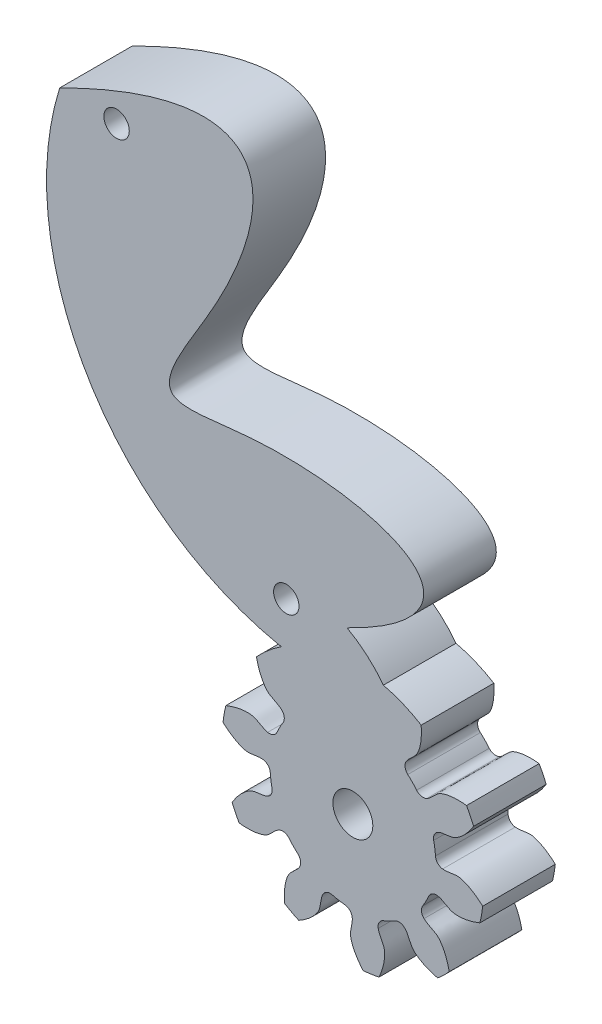
SolidWorks part; units mm, degrees
material "3003 Alaşım"
ref_plane "前视基准面" through (0, 0, 0) normal (0, 0, 1) x (1, 0, 0)
ref_plane "上视基准面" through (0, 0, 0) normal (0, 1, 0) x (1, 0, 0)
ref_plane "右视基准面" through (0, 0, 0) normal (1, 0, 0) x (0, 0, -1)
sketch "草图1" plane through (0, 0, 0) normal (0, 0, 1) x (1, 0, 0)
  line L0 (-50, 0) -> (-25, 0) construction
  line L1 (-28.7348, 74.7114) -> (-28.7348, -58.328) construction
  line L31 (-28.7348, -54.9949) -> (-28.7348, -58.328)
  line L34 (-28.7348, -66.107) -> (-16.1671, -66.107) construction
  arc A16 (-32.5692, -50.9983) -> (-62.8387, 0.35) centre (-24.3784, -11.5738) cw
  arc A17 (-23.252, -44.2645) -> (-15.0404, -59.3926) centre (-31.0005, -58.2631) cw
  arc A18 (-28.7348, -58.328) -> (-15.0404, -59.3926) centre (-22.4509, -66.107) ccw
  arc A20 (-32.5692, -50.9983) -> (-28.7348, -54.9949) centre (-32.7348, -54.9949) cw
  circle A22 centre (-22.4509, -66.107) radius 5
  circle A26 centre (-31.6201, -45.0019) radius 1.75
  circle A27 centre (-55, 0) radius 1.75
  spline S0 degree 3 poles (-62.8387, 0.35) (-32.3892, 15.6125) (-31.8503, -2.5111) (-51.8071, -30.7499) (-24.5472, -25.1943) (-0.1216, -33.0016) (-23.252, -44.2645) knots 0 0 0 0 0.423155 0.543124 0.634591 1 1 1 1
  point P9 (-25, 0)
  point P64 (-28.7348, -52.6717)
  point P69 (-2.507, 0.35)
  dimension "D4" = 3.5
  dimension "D6" = 16
  dimension "D7" = 4
  dimension "D9" = 10
  dimension "D10" = 3.5
  dimension "D3" = 25
extrude "凸台拉伸1" add sketch "草图1" along normal blind 1
extrude "凸台-拉伸1" add sketch "草图1<2>" along normal blind 10
sketch "草图1<2>" plane through (0, 0, 0) normal (0, 0, 1) x (1, 0, 0) same geometry as "草图1"
sketch "草图7" plane through (0, 0, 0) normal (0, 0, 1) x (1, 0, 0)
  line L0 (-22.4509, -66.107) -> (-22.4509, -48.107) construction
  arc A0 (-32.0748, -59.9963) -> (-32.8986, -61.5456) centre (-22.4509, -66.107) ccw
  arc A1 (-35.9543, -51.7661) -> (-41.8911, -62.9316) centre (-22.4509, -66.107) ccw
  arc A2 (-32.8986, -61.5456) -> (-34.1894, -62.2026) centre (-33.9434, -61.0895) cw
  arc A3 (-32.2519, -58.5588) -> (-32.0748, -59.9963) centre (-33.0372, -59.3852) cw
  circle A4 centre (-22.4509, -66.107) radius 14.5222 construction
  circle A5 centre (-22.4509, -66.107) radius 18 construction
  circle A6 centre (-22.4509, -66.107) radius 11.4 construction
  circle A7 centre (-22.4509, -66.107) radius 15 construction
  spline S0 degree 3 poles (-32.2519, -58.5588) (-32.7705, -58.066) (-33.6057, -57.8737) (-34.2019, -57.3264) (-34.2828, -57.24) (-34.3453, -57.1694) (-34.4147, -57.0856) (-34.4903, -56.9882) (-34.5713, -56.8768) (-34.657, -56.7509) (-34.7464, -56.6101) (-34.8387, -56.4541) (-34.9331, -56.2825) (-35.0285, -56.0951) (-35.1242, -55.8917) (-35.2192, -55.6721) (-35.3125, -55.436) (-35.4032, -55.1835) (-35.4903, -54.9145) (-35.573, -54.6289) (-35.6502, -54.3268) (-35.721, -54.0082) (-35.7843, -53.6733) (-35.8393, -53.3223) (-35.885, -52.9553) (-35.9331, -52.4354) (-35.9506, -52.0368) (-35.9543, -51.7661) knots 0.111786 0.111786 0.111786 0.111786 0.344236 0.363717 0.372294 0.382431 0.394128 0.407384 0.422199 0.438574 0.456508 0.476002 0.497056 0.519669 0.543841 0.569573 0.596865 0.625716 0.656126 0.688097 0.721626 0.756715 0.793364 0.831572 0.87134 0.912667 1 1 1 1
  spline S1 degree 3 poles (-34.1894, -62.2026) (-34.8879, -62.0482) (-35.5143, -61.4634) (-36.3015, -61.2751) (-36.4184, -61.2564) (-36.5119, -61.2441) (-36.6201, -61.2334) (-36.7431, -61.2252) (-36.8808, -61.2203) (-37.0331, -61.2197) (-37.1998, -61.2243) (-37.3808, -61.235) (-37.5758, -61.2527) (-37.7845, -61.2783) (-38.0066, -61.3128) (-38.2418, -61.3569) (-38.4897, -61.4115) (-38.7498, -61.4775) (-39.0215, -61.5557) (-39.3045, -61.6469) (-39.5982, -61.7518) (-39.9018, -61.8713) (-40.2149, -62.006) (-40.5367, -62.1567) (-40.8665, -62.3241) (-41.3244, -62.5749) (-41.6646, -62.7833) (-41.8911, -62.9316) knots 0.111786 0.111786 0.111786 0.111786 0.344236 0.363717 0.372294 0.382431 0.394128 0.407384 0.422199 0.438574 0.456508 0.476002 0.497056 0.519669 0.543841 0.569573 0.596865 0.625716 0.656126 0.688097 0.721626 0.756715 0.793364 0.831572 0.87134 0.912667 1 1 1 1
  dimension "D1" = 1.14
  dimension "Db" = 29.0444
  dimension "Da" = 36
  dimension "Df" = 22.8
  dimension "Dn" = 30
sketch "草图8" plane through (0, 0, 10) normal (0, 0, 1) x (1, 0, 0)
  circle A0 centre (-22.4509, -66.107) radius 18
extrude "凸台-拉伸3" add sketch "草图8" against normal blind 10
sketch "草图9" plane through (0, 0, 10) normal (0, 0, 1) x (1, 0, 0)
  circle A0 centre (-22.4509, -66.107) radius 2.75
  dimension "D1" = 5.5
extrude "切除-拉伸3" cut sketch "草图7" along normal blind 10
extrude "切除-拉伸4" cut sketch "草图9" against normal blind 10
pattern_circular "阵列(圆周)3" count 8 every 36 about axis through (-22.4509, -66.107, 0) along (0, 0, 1) of "切除-拉伸3"
